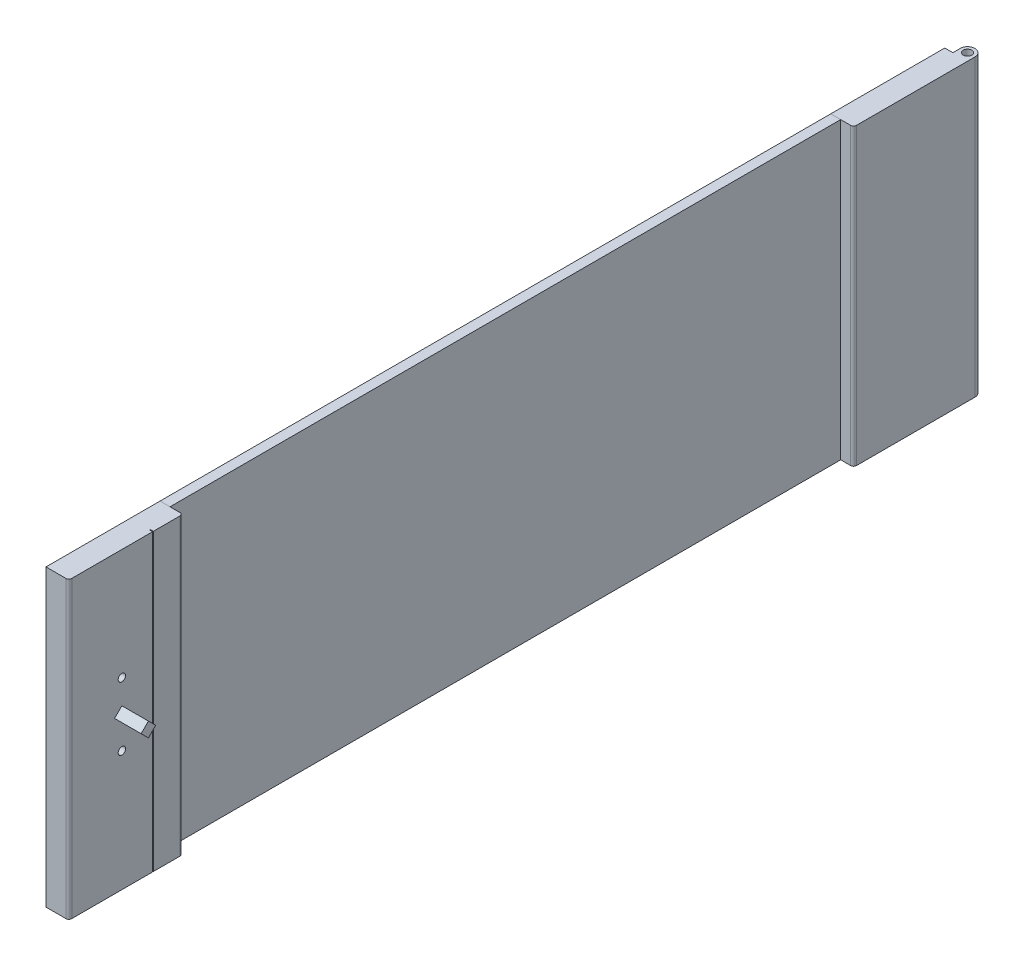
SolidWorks part; units mm, degrees
ref_plane "Front" through (0, 0, 0) normal (0, 0, 1) x (1, 0, 0)
ref_plane "Top" through (0, 0, 0) normal (0, 1, 0) x (1, 0, 0)
ref_plane "Right" through (0, 0, 0) normal (1, 0, 0) x (0, 0, -1)
sketch "Эскиз1" plane through (0, 0, 0) normal (0, 1, 0) x (1, 0, 0)
  line L0 (134.0325, 108.8481) -> (147.5325, 108.8481)
  line L1 (134.0325, -423.7519) -> (147.5325, -423.7519)
  line L2 (134.0325, -423.7519) -> (134.0325, -346.3519)
  line L3 (134.0325, -346.3519) -> (147.5325, -346.3519)
  line L4 (149.5325, -421.7519) -> (149.5325, -366.9519)
  line L5 (134.0325, 108.8481) -> (134.0325, 186.2481)
  line L6 (134.0325, 186.2481) -> (139.5325, 186.2481)
  line L7 (149.5325, 110.8481) -> (149.5325, 184.2481)
  line L8 (139.5325, 191.2481) -> (139.5325, 186.2481)
  line L9 (149.5325, 191.2481) -> (149.5325, 184.2481)
  line L10 (149.5325, -366.4519) -> (149.5325, -348.3519)
  line L11 (149.5325, -366.4519) -> (147.5325, -366.4519)
  line L13 (149.5325, -366.9519) -> (147.5325, -366.9519)
  line L14 (147.5325, -366.4519) -> (147.5325, -366.9519)
  arc A0 (149.5325, 191.2481) -> (139.5325, 191.2481) centre (144.5325, 191.2481) ccw
  arc A2 (147.5325, 108.8481) -> (149.5325, 110.8481) centre (147.5325, 110.8481) ccw
  arc A3 (147.5325, -423.7519) -> (149.5325, -421.7519) centre (147.5325, -421.7519) ccw
  arc A4 (147.5325, -346.3519) -> (149.5325, -348.3519) centre (147.5325, -348.3519) cw
  circle A5 centre (144.5325, 191.2481) radius 2.9319
  point P18 (149.5325, -423.7519)
  point P21 (149.5325, -346.3519)
  dimension "D3" = 10
  dimension "D5" = 0.5
  dimension "D1" = 15.5
  dimension "D2" = 77.4
  dimension "D4" = 615
  dimension "D6" = 2
  dimension "D7" = 20.1
extrude "Бобышка-Вытянуть1" add sketch "Эскиз1" along normal blind 200
sketch "Эскиз2" plane through (0, 200, 0) normal (0, 1, 0) x (1, 0, 0)
  line L0 (134.0325, 108.8481) -> (147.5325, 108.8481) construction
  line L1 (134.0325, -346.3519) -> (140.7825, -346.3519)
  line L2 (134.0325, -346.3519) -> (134.0325, 108.8481)
  line L3 (134.0325, 108.8481) -> (140.7825, 108.8481)
  line L4 (140.7825, -346.3519) -> (140.7825, 108.8481)
extrude "Бобышка-Вытянуть2" add sketch "Эскиз2" against normal blind 200 separate body
sketch "Эскиз3" plane through (149.5325, 0, 0) normal (1, 0, 0) x (0, 0, -1)
  line L0 (-423.7519, 200) -> (-423.7519, 0) construction
  line L1 (-392.7017, 103.1726) -> (-387.7519, 108.1224)
  line L2 (-392.7017, 103.1726) -> (-387.7519, 98.2229)
  line L3 (-387.7519, 98.2229) -> (-382.8022, 103.1726)
  line L4 (-387.7519, 108.1224) -> (-382.8022, 103.1726)
  line L5 (-392.7017, 103.1726) -> (-382.8022, 103.1726) construction
  line L6 (-387.7519, 98.2229) -> (-387.7519, 108.1224) construction
  line L8 (-399.1728, 103.1726) -> (-378.6499, 103.1726) construction
  circle A0 centre (-387.7519, 124.6726) radius 2.5
  circle A1 centre (-387.7519, 81.6726) radius 2.5
  point P0 (-387.7519, 103.1726)
  dimension "D2" = 5
  dimension "D1" = 36
  dimension "D3" = 43
extrude "Бобышка-Вытянуть3" add sketch "Эскиз3" along normal blind 18 contours L4 L1 L2 L3 region at (149.5325, 103.1726, 387.7519)
extrude "Вырез-Вытянуть1" cut sketch "Эскиз3<3>" against normal blind 5 contours A0 | A1 region at (149.5325, 124.6726, 387.7519) region at (149.5325, 81.6726, 387.7519)
sketch "Эскиз3<3>" plane through (149.5325, 0, 0) normal (1, 0, 0) x (0, 0, -1) same geometry as "Эскиз3"
